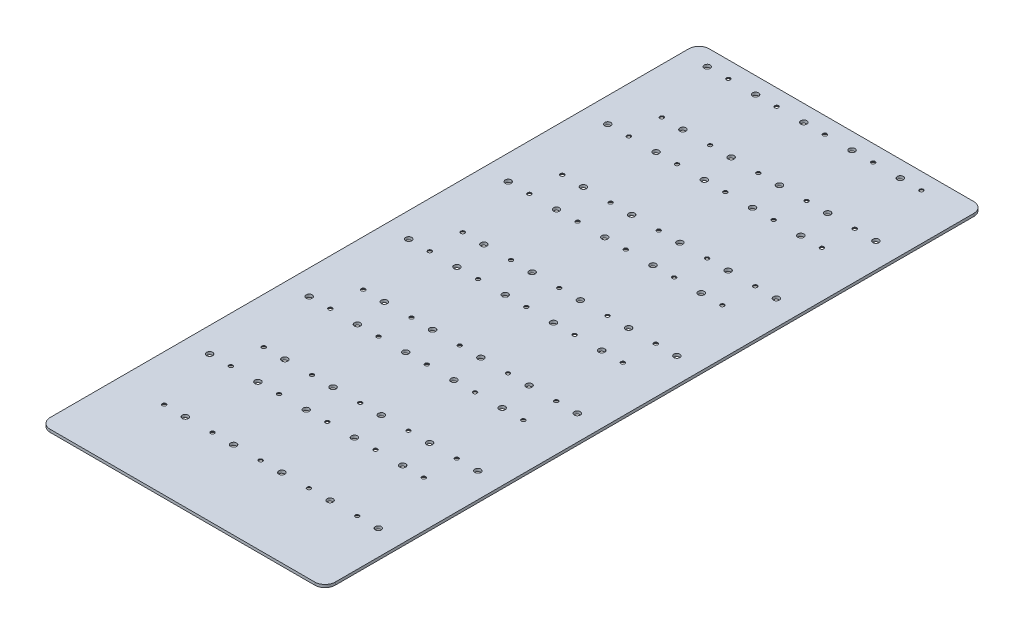
SolidWorks part; units mm, degrees
material "6061 Alloy"
ref_plane "Front Plane" through (0, 0, 0) normal (0, 0, 1) x (1, 0, 0)
ref_plane "Top Plane" through (0, 0, 0) normal (0, 1, 0) x (1, 0, 0)
ref_plane "Right Plane" through (0, 0, 0) normal (1, 0, 0) x (0, 0, -1)
sketch "Sketch1" plane through (0, 0, 0) normal (0, 1, 0) x (1, 0, 0)
  line L0 (0, 289.1112) -> (0, -190.8961) construction
  line L1 (-155.8829, 0) -> (238.1281, 0) construction
  line L8 (118.15, 273.15) -> (-118.15, 273.15)
  line L9 (-118.15, 273.15) -> (-118.15, -273.15)
  line L10 (-118.15, -273.15) -> (118.15, -273.15)
  line L11 (118.15, -273.15) -> (118.15, 273.15)
  dimension "D1" = 546.3
  dimension "D2" = 236.3
extrude "Boss-Extrude1" add sketch "Sketch1" along normal blind 2.286
sketch "Sketch2" plane through (0, 2.286, 0) normal (0, 1, 0) x (1, 0, 0)
  circle A0 centre (-97.61, 259.5) radius 2.5
  circle A1 centre (-80.11, 259.5) radius 1.6
  circle A2 centre (-62.61, 204.3) radius 2.5
  circle A3 centre (-80.11, 204.3) radius 1.6
  dimension "D1" = 3.2
  dimension "D2" = 3.2
  dimension "D3" = 5
  dimension "D4" = 5
extrude "Cut-Extrude1" cut sketch "Sketch2" against normal through all both
chamfer "Chamfer1" distance 1.8 2 edges at (-80.11, 0, -257.9) (-80.11, 0, -202.7)
pattern_linear "LPattern3" count 6 spacing 82.5 along (0, 0, 1) count 5 spacing 40 along (1, 0, 0) of "Chamfer1", "Cut-Extrude1"
fillet "Fillet1" radius 8.5 4 edges at (118.15, 1.143, -273.15) (-118.15, 1.143, 273.15) (118.15, 1.143, 273.15) (-118.15, 1.143, -273.15)
